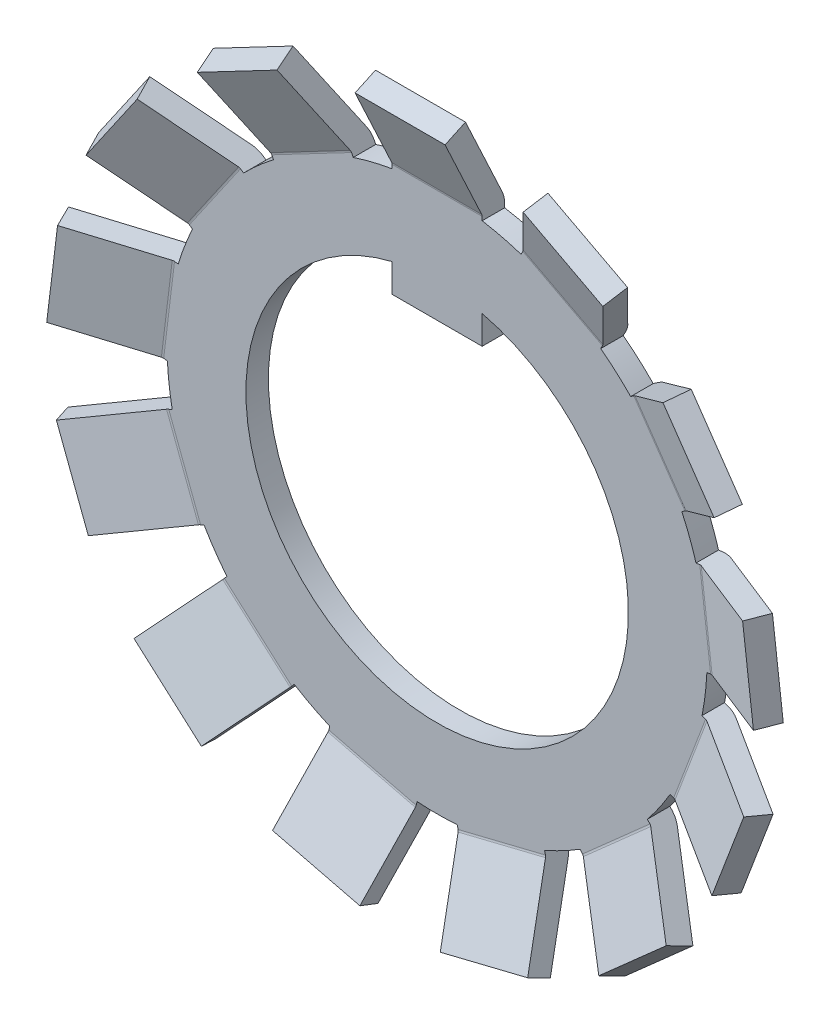
SolidWorks part; units mm, degrees
material "Handl."
ref_plane "Płaszczyzna przednia" through (0, 0, 0) normal (0, 0, 1) x (1, 0, 0)
ref_plane "Płaszczyzna górna" through (0, 0, 0) normal (0, 1, 0) x (1, 0, 0)
ref_plane "Płaszczyzna prawa" through (0, 0, 0) normal (1, 0, 0) x (0, 0, -1)
sketch "Szkic1" plane through (0, 0, 0) normal (0, 0, 1) x (1, 0, 0)
  circle A0 centre (0, 0) radius 8.5
  circle A1 centre (0, 0) radius 12
  dimension "D1" = 24
  dimension "D2" = 17
extrude "Dodanie-wyciągnięcie2" add sketch "Szkic1" along normal blind 1
sketch "Szkic6" plane through (0, 0, 0) normal (1, 0, 0) x (0, 0, -1)
  line L0 (-1, 11.5) -> (0, 11.5)
  line L1 (-1, 12) -> (-1, -12) construction
  line L2 (0, -12) -> (0, 12) construction
  line L3 (0, 11.5) -> (0, 12)
  line L4 (-0.1124, 12.5071) -> (-1.7412, 16)
  line L5 (-1.7412, 16) -> (-2.6475, 15.5774)
  line L6 (-2.6475, 15.5774) -> (-1.0187, 12.0845)
  line L7 (-1, 12) -> (-1, 11.5)
  line L8 (0, 0) -> (-1, 0) construction
  arc A0 (0, 12) -> (-0.1124, 12.5071) centre (-1.2, 12) ccw
  arc A1 (-1.0187, 12.0845) -> (-1, 12) centre (-1.2, 12) cw
  dimension "D1" = 0.2
  dimension "D2" = 0.5
  dimension "D3" = 25
  dimension "D4" = 32
extrude "Dodanie-wyciągnięcie3" add sketch "Szkic6" along normal mid plane 4
pattern_circular "Szyk kołowy1" count 13 over 360 about axis through (0, 0, 1) along (0, 0, -1) of "Dodanie-wyciągnięcie3"
sketch "Szkic7" plane through (0, 0, 1) normal (0, 0, 1) x (1, 0, 0)
  line L1 (-2, 8.5) -> (2, 8.5)
  line L2 (-2, 8.5) -> (-2, 7)
  line L3 (-2, 7) -> (2, 7)
  line L4 (2, 8.5) -> (2, 7)
  circle A1 centre (0, 0) radius 8.5 construction
  point P4 (0, 7)
  dimension "D1" = 4
  dimension "D2" = 15.5
extrude "Dodanie-wyciągnięcie4" add sketch "Szkic7" against normal up to surface (1 mm away) up to face at (0, 0, 0)
